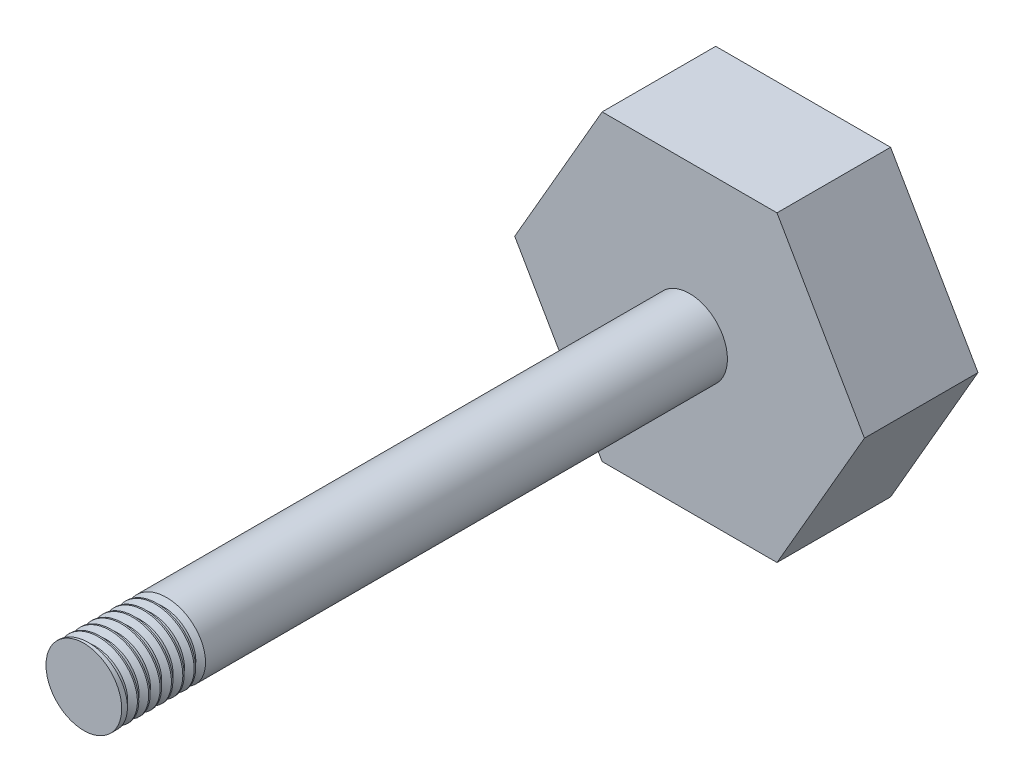
SolidWorks part; units mm, degrees
ref_plane "Front Plane" through (0, 0, 0) normal (0, 0, 1) x (1, 0, 0)
ref_plane "Top Plane" through (0, 0, 0) normal (0, 1, 0) x (1, 0, 0)
ref_plane "Right Plane" through (0, 0, 0) normal (1, 0, 0) x (0, 0, -1)
sketch "Sketch1" plane through (0, 0, 0) normal (0, 0, 1) x (1, 0, 0)
  line L1 (11.547, 20) -> (-11.547, 20)
  line L2 (-11.547, 20) -> (-23.094, 0)
  line L3 (-23.094, 0) -> (-11.547, -20)
  line L4 (-11.547, -20) -> (11.547, -20)
  line L5 (11.547, -20) -> (23.094, 0)
  line L6 (23.094, 0) -> (11.547, 20)
  circle A0 centre (0, 0) radius 20 construction
extrude "Boss-Extrude1" add sketch "Sketch1" along normal blind 15
sketch "Sketch2" plane through (0, 0, 15) normal (0, 0, 1) x (1, 0, 0)
  circle A0 centre (0, 0) radius 5
extrude "Boss-Extrude2" add sketch "Sketch2" along normal blind 80
thread "Thread1" pitch 1.5 method cut profile "Thread Profile1" start angle 0, offset 0, length 10, pitch 1.5, diameter 10
ref_plane "Plane1" through (-5, 0, 95) normal (0, -1, 0) x (-1, 0, 0)
sketch "Thread Profile1" plane through (-5, 0, 95) normal (0, -1, 0) x (-1, 0, 0)
  line L0 (0, 0) -> (0, 1.5) construction
  line L11 (0, 0) -> (0, 1.3125)
  line L12 (0, 1.3125) -> (-0.8119, 0.8437)
  line L13 (-0.8119, 0.8437) -> (-0.8119, 0.4687)
  line L15 (-0.8119, 0.4687) -> (0, 0)
  line L17 (-0.8119, 0.6562) -> (0, 0.6562) construction
  point P2 (0, 0)
  dimension "Pitch" = 1.5
  dimension "Profile_Angle" = 60
  dimension "Profile_Land" = 0.375
  dimension "Profile_Height" = 0.8119
